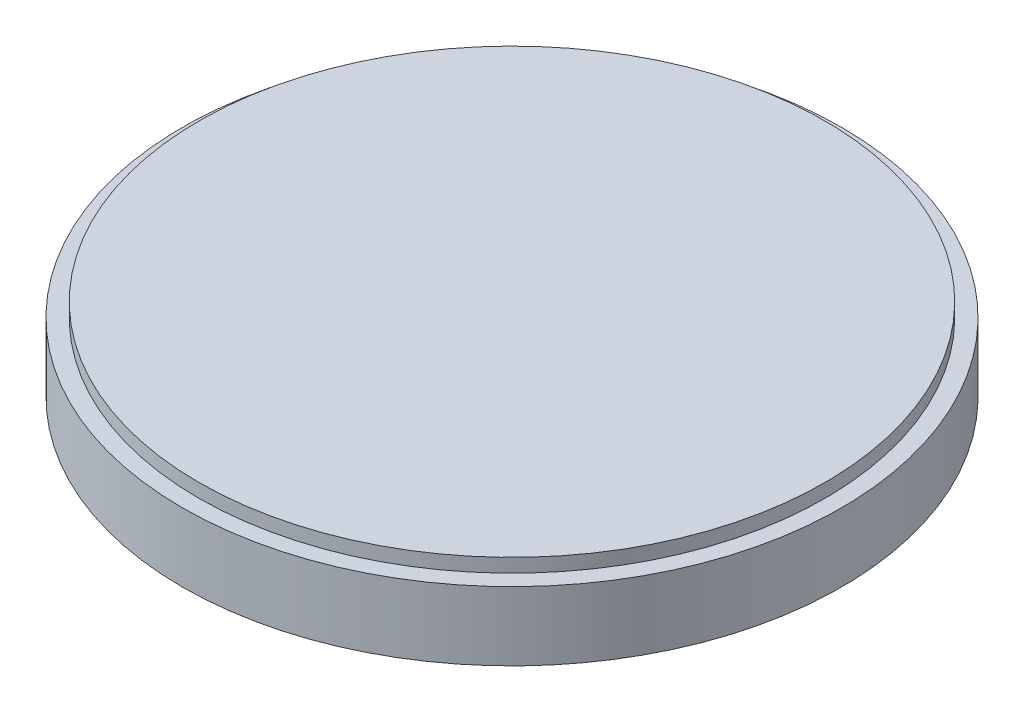
SolidWorks part; units mm, degrees
ref_plane "Front Plane" through (0, 0, 0) normal (0, 0, 1) x (1, 0, 0)
ref_plane "Top Plane" through (0, 0, 0) normal (0, 1, 0) x (1, 0, 0)
ref_plane "Right Plane" through (0, 0, 0) normal (1, 0, 0) x (0, 0, -1)
sketch "Sketch1" plane through (0, 0, 0) normal (0, 1, 0) x (1, 0, 0)
  circle A0 centre (0, 0) radius 57
  circle A1 centre (0, 0) radius 60
  dimension "D1" = 120
  dimension "D2" = 114
extrude "Extrude4" add sketch "Sketch1" along normal mid plane 15 contours A0
extrude "Extrude5" add sketch "Sketch" against normal up to surface (7.5 mm away) and the other way blind 5 up to face at (0, -7.5, 57)
sketch "Sketch" plane through (0, 0, 0) normal (0, 1, 0) x (1, 0, 0) same geometry as "Sketch1"
